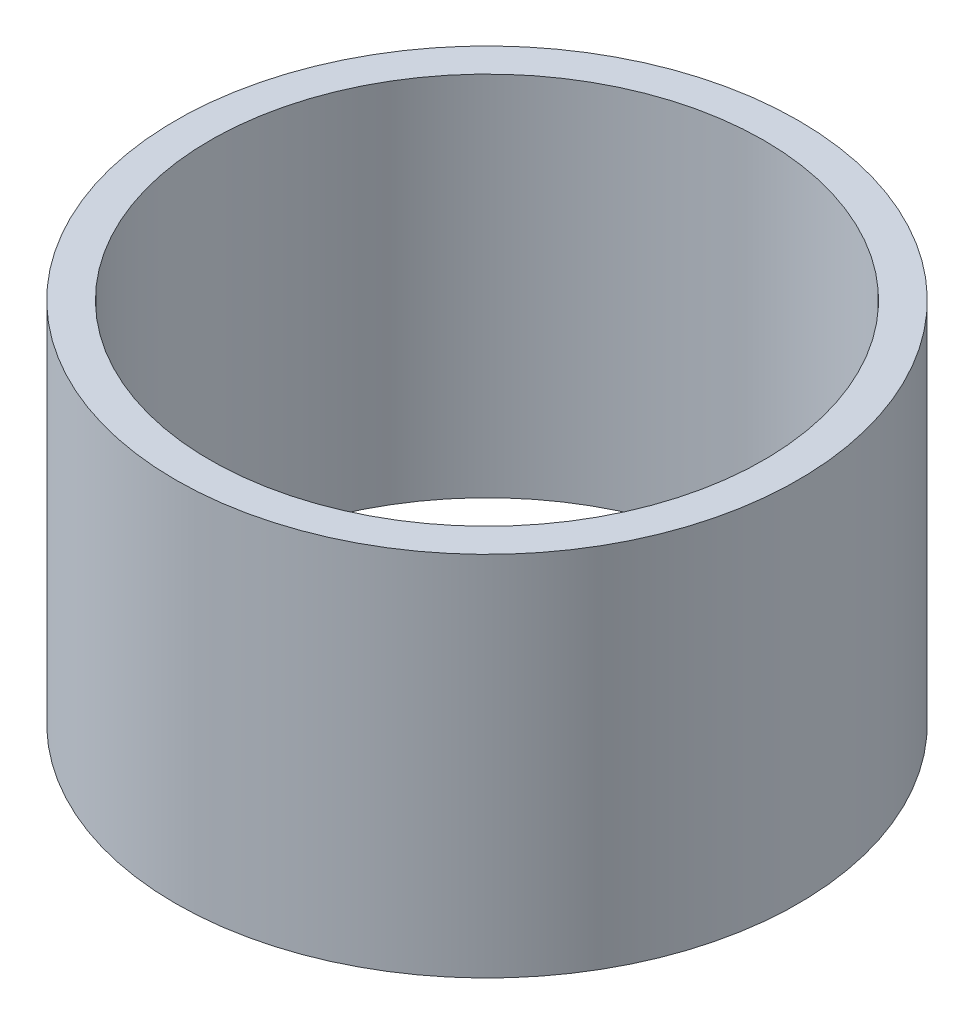
SolidWorks part; units mm, degrees
ref_plane "Front Plane" through (0, 0, 0) normal (0, 0, 1) x (1, 0, 0)
ref_plane "Top Plane" through (0, 0, 0) normal (0, 1, 0) x (1, 0, 0)
ref_plane "Right Plane" through (0, 0, 0) normal (1, 0, 0) x (0, 0, -1)
sketch "Sketch1" plane through (0, 0, 0) normal (0, 1, 0) x (1, 0, 0)
  circle A0 centre (0, 0) radius 50
  dimension "SLEEVE_OD" = 100
extrude "Boss-Extrude1" add sketch "Sketch1" along normal blind 58.9222
sketch "Sketch2" plane through (0, 0, 0) normal (0, 1, 0) x (1, 0, 0)
  circle A0 centre (0, 0) radius 44.4689
  dimension "BORE_D" = 88.9377
extrude "Cut-Extrude1" cut sketch "Sketch2" along normal through all
chamfer "Chamfer1" distance 3.6153 angle 30 rebuild error yes
